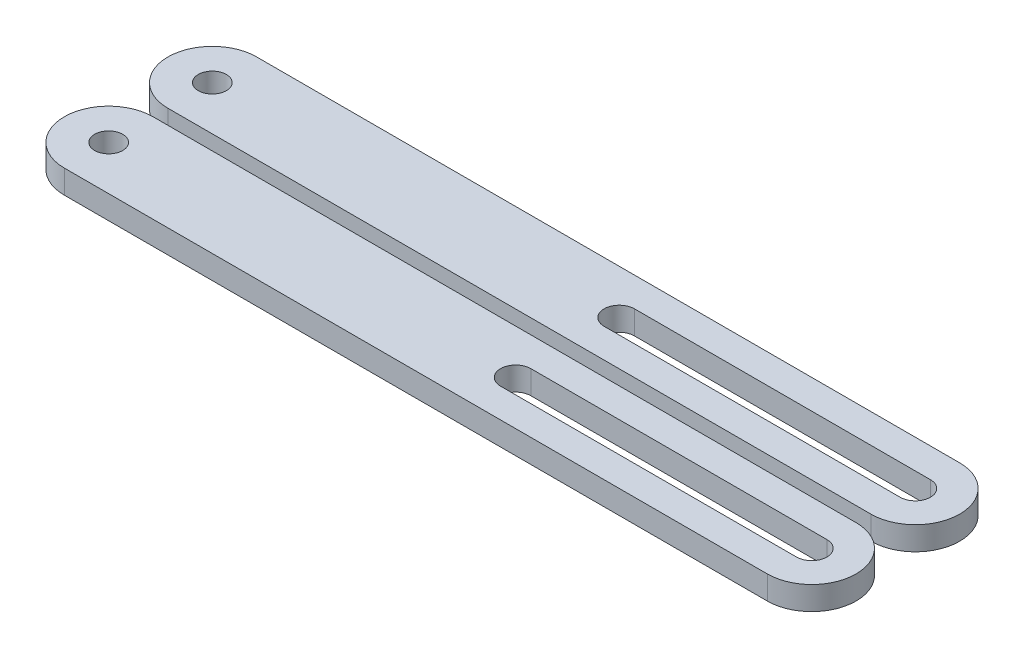
SolidWorks part; units mm, degrees
ref_plane "Front Plane" through (0, 0, 0) normal (0, 0, 1) x (1, 0, 0)
ref_plane "Top Plane" through (0, 0, 0) normal (0, 1, 0) x (1, 0, 0)
ref_plane "Right Plane" through (0, 0, 0) normal (1, 0, 0) x (0, 0, -1)
sketch "Sketch1" plane through (0, 0, 0) normal (0, 1, 0) x (1, 0, 0)
  line L0 (0, 0) -> (100, 0) construction
  line L4 (55, 0) -> (95, 0) construction
  line L5 (55, 2.05) -> (95, 2.05)
  line L6 (55, -2.05) -> (95, -2.05)
  line L7 (0, 0) -> (95, 0) construction
  line L8 (0, 6) -> (95, 6)
  line L9 (0, -6) -> (95, -6)
  circle A1 centre (0, 0) radius 1.9
  arc A2 (0, -6) -> (0, 6) centre (0, 0) ccw construction
  arc A3 (55, 2.05) -> (55, -2.05) centre (55, 0) ccw
  arc A4 (95, -2.05) -> (95, 2.05) centre (95, 0) ccw
  circle A5 centre (0, 0) radius 11.725 construction
  arc A8 (0, 6) -> (0, -6) centre (0, 0) ccw
  arc A9 (95, -6) -> (95, 6) centre (95, 0) ccw
  point P4 (0, 6)
  point P11 (75, 0)
  point P17 (47.5, 0)
  dimension "D1" = 3.8
  dimension "D2" = 12
  dimension "D5" = 4.1
  dimension "D9" = 23.45
  dimension "D4" = 100
  dimension "D6" = 40
  dimension "D7" = 5
extrude "Boss-Extrude1" add sketch "Sketch1" along normal blind 3.175
sketch "Sketch2" plane through (0, 0, 0) normal (0, 1, 0) x (1, 0, 0)
  line L0 (0, 16.069) -> (0, 0)
  line L1 (0, 0) -> (63.4626, 0)
pattern_linear "LPattern1" count 2 spacing 14 along (0, 0, -1) of bodies 101
